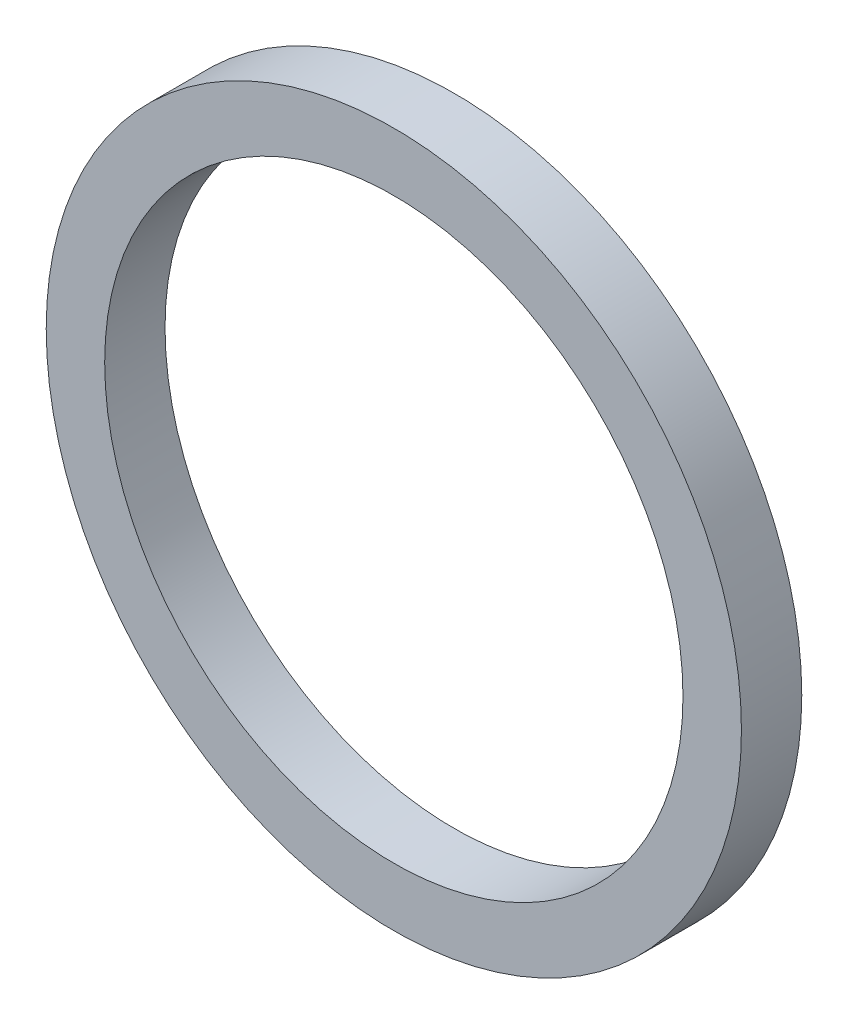
SolidWorks part; units mm, degrees
material "ABS PC"
ref_plane "Alzado" through (0, 0, 0) normal (0, 0, 1) x (1, 0, 0)
ref_plane "Planta" through (0, 0, 0) normal (0, 1, 0) x (1, 0, 0)
ref_plane "Vista lateral" through (0, 0, 0) normal (1, 0, 0) x (0, 0, -1)
sketch "Croquis1" plane through (0, 0, 0) normal (0, 0, 1) x (1, 0, 0)
  line L0 (-35.9552, 4.3557) -> (-18.8079, 20.2678) construction
  line L1 (-35.9552, 4.3557) -> (-18.8079, 20.2678)
  line L2 (-33.5, -5) -> (-27.1942, -5) construction
  line L3 (33.5, 0) -> (33.5, 27.3668) construction
  line L5 (-33.5, -5) -> (-27.1942, -5)
  line L6 (0, 0) -> (33.5, 0) construction
  line L9 (30.214, 17.2839) -> (40.6092, 7.7576)
  line L10 (30.214, 17.2839) -> (25.0675, 11.668)
  line L11 (33.5, 0) -> (40.6092, 7.7576)
  arc A0 (-35.9552, 4.3557) -> (-33.5, -5) centre (-33.5, 0) ccw construction
  arc A1 (-27.1942, -5) -> (18.8387, -20.2392) centre (0, 0) ccw
  arc A3 (33.5, -5) -> (36.8806, 3.684) centre (33.5, 0) ccw construction
  circle A4 centre (-33.5, 0) radius 2.25 construction
  circle A5 centre (33.5, 0) radius 2.25 construction
  arc A6 (-35.9552, 4.3557) -> (-33.5, -5) centre (-33.5, 0) ccw
  circle A7 centre (0, 0) radius 27.65 construction
  arc A8 (25.0675, 11.668) -> (-18.8079, 20.2678) centre (0, 0) ccw
  arc A9 (38.3821, -1.0792) -> (36.8781, 3.6862) centre (33.5, 0) ccw
  circle A10 centre (-33.5, 0) radius 2.25
  circle A11 centre (33.5, 0) radius 2.25
  point P8 (0, 0)
  dimension "D1" = 14.1
  dimension "D2" = 42.503
  dimension "D3" = 7.7576
extrude "Saliente-Extruir1" add sketch "Croquis1" along normal blind 7.4 rebuild error yes
sketch "Croquis2" plane through (0, 0, 7.4) normal (0, 0, 1) x (1, 0, 0)
  circle A3 centre (0, 0) radius 20.5
  dimension "D1" = 41
extrude "Cortar-Extruir1" cut sketch "Croquis2" against normal through all contours A3 rebuild error yes
sketch "Croquis3" plane through (0, 0, 7.4) normal (0, 0, 1) x (1, 0, 0)
  circle A1 centre (0, 0) radius 23
  circle A2 centre (0, 0) radius 27.65 construction
  circle A3 centre (0, 0) radius 27.65
  dimension "D1" = 46
extrude "Saliente-Extruir2" add sketch "Croquis3" along normal blind 4.8
